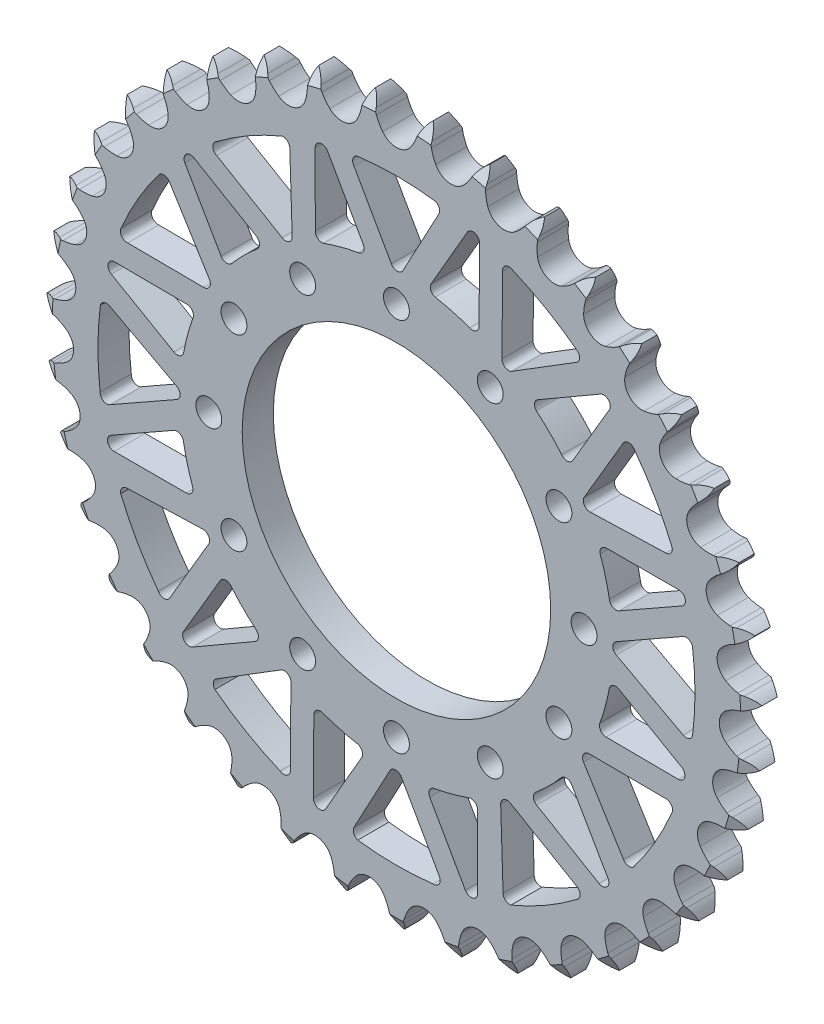
SolidWorks part; units mm, degrees
material "7075-T6 (SN)"
ref_plane "Front Plane" through (0, 0, 0) normal (0, 0, 1) x (1, 0, 0)
ref_plane "Top Plane" through (0, 0, 0) normal (0, 1, 0) x (1, 0, 0)
ref_plane "Right Plane" through (0, 0, 0) normal (1, 0, 0) x (0, 0, -1)
sketch "Work Sketch" plane through (0, 0, 0) normal (0, 0, 1) x (1, 0, 0)
  line L0 (0, 0) -> (0, 160.4542) construction
  line L1 (-112.0919, 78.9148) -> (87.2579, 78.9148) construction
  line L2 (5.102, 120.8822) -> (5.102, 112.9699) construction
  line L3 (-12.8497, 82.6953) -> (16.7256, 82.6953) construction
  line L4 (5.102, 82.6953) -> (-6.0879, 74.4036) construction
  line L5 (5.102, 82.6953) -> (-4.6505, 79.1506) construction
  line L6 (-4.6505, 79.1506) -> (-6.8863, 85.3019)
  line L7 (-11.5114, 78.0206) -> (-7.1525, 78.0206) construction
  line L8 (-11.0765, 124.7602) -> (-11.0765, 110.2345) construction
  line L9 (0, 0) -> (-3.4402, 42.6146) construction
  circle A0 centre (0, 0) radius 78.9148
  circle A1 centre (0, 78.9148) radius 4.0088
  arc A2 (-4.6505, 79.1506) -> (-3.2209, 76.5281) centre (5.0804, 82.7541) ccw
  circle A3 centre (-11.0765, 78.0206) radius 6.4254
  point P23 (-3.2209, 76.5281)
  dimension "D1" = 157.8295
  dimension "D8" = 10.3767
  dimension "D2" = 8.0177
  dimension "D3" = 5.102
  dimension "D4" = 3.7806
  dimension "D5" = 36.538
  dimension "D6" = 16.564
  dimension "D7" = 10.3767
  dimension "D9" = 0.8942
  dimension "D10" = 11.0765
  dimension "D11" = 4.615
sketch "Teeth Sketch" plane through (0, 0, 0) normal (0, 0, 1) x (1, 0, 0)
  line L0 (5.0376, 80.2155) -> (4.6505, 79.1506)
  line L1 (-7.4865, 92.7372) -> (-4.7839, 59.2593) construction
  line L2 (0, 0) -> (-10.9133, 132.3061) construction
  line L3 (7.8951, 79.9848) -> (8.1063, 78.8717)
  line L4 (16093.3137, -199351.4616) -> (-16096.7539, 199394.0762) construction
  line L5 (0, 146.3285) -> (0, 56.9858) construction
  line L6 (17.8398, 78.3686) -> (17.287, 77.3797)
  line L7 (0, -200000) -> (0, 200160.4542) construction
  line L8 (20.6234, 77.6826) -> (20.6533, 76.5499)
  line L9 (-4.6505, 79.1506) -> (-6.8863, 85.3019) construction
  line L10 (44.1616, 67.154) -> (43.8313, 66.0702)
  line L11 (-5.0376, 80.2155) -> (-4.6505, 79.1506)
  line L12 (30.18, 74.4921) -> (29.4757, 73.6046)
  line L13 (32.8175, 73.3684) -> (32.6653, 72.2456)
  line L14 (41.7385, 68.6862) -> (40.901, 67.9232)
  line L15 (52.2161, 61.1014) -> (51.267, 60.4826)
  line L16 (54.362, 59.2003) -> (53.8621, 58.1836)
  line L17 (61.3413, 51.9341) -> (60.3052, 51.4756)
  line L18 (63.1544, 49.7134) -> (62.4979, 48.79)
  line L19 (68.8777, 41.4218) -> (67.7815, 41.1354)
  line L20 (70.3112, 38.939) -> (69.515, 38.1328)
  line L21 (74.6303, 29.8366) -> (73.5023, 29.7298)
  line L22 (75.6469, 27.156) -> (74.7318, 26.488)
  line L23 (78.45, 17.4787) -> (77.3195, 17.5542)
  line L24 (79.0234, 14.6698) -> (78.013, 14.1572)
  line L25 (80.2378, 4.6681) -> (79.1341, 4.9239)
  line L26 (80.3533, 1.8035) -> (79.2737, 1.4597)
  line L27 (79.9476, -8.2634) -> (78.8992, -7.8338)
  line L28 (79.602, -11.1094) -> (78.4813, -11.2756)
  line L29 (77.5867, -20.9809) -> (76.6208, -20.3887)
  line L30 (76.7891, -23.7346) -> (75.6562, -23.7189)
  line L31 (73.2164, -33.155) -> (72.358, -32.4155)
  line L32 (71.9874, -35.7451) -> (70.8717, -35.5478)
  line L33 (66.9499, -44.4704) -> (66.2212, -43.6028)
  line L34 (65.3213, -46.8298) -> (64.2517, -46.4561)
  line L35 (58.9493, -54.634) -> (58.3693, -53.6608)
  line L36 (56.9634, -56.7016) -> (55.9676, -56.1612)
  line L37 (49.422, -63.3827) -> (49.0056, -62.329)
  line L38 (47.1301, -65.1049) -> (46.2339, -64.4118)
  line L39 (38.6147, -70.4897) -> (38.3727, -69.3829)
  line L40 (36.0763, -71.822) -> (35.3028, -70.9941)
  line L41 (26.8073, -75.7712) -> (26.746, -74.6398)
  line L42 (24.088, -76.679) -> (23.4574, -75.7377)
  line L43 (14.3056, -79.0901) -> (14.4266, -77.9636)
  line L44 (11.4759, -79.55) -> (11.0044, -78.5198)
  line L45 (1.4334, -80.3607) -> (1.7335, -79.2682)
  line L46 (-1.4334, -80.3607) -> (-1.7335, -79.2682)
  line L47 (-11.4759, -79.55) -> (-11.0044, -78.5198)
  line L48 (-14.3056, -79.0901) -> (-14.4266, -77.9636)
  line L49 (-24.088, -76.679) -> (-23.4574, -75.7377)
  line L50 (-26.8073, -75.7712) -> (-26.746, -74.6398)
  line L51 (-36.0763, -71.822) -> (-35.3028, -70.9941)
  line L52 (-38.6147, -70.4897) -> (-38.3727, -69.3829)
  line L53 (-47.1301, -65.1049) -> (-46.2339, -64.4118)
  line L54 (-49.422, -63.3827) -> (-49.0056, -62.329)
  line L55 (-56.9634, -56.7016) -> (-55.9676, -56.1612)
  line L56 (-58.9493, -54.634) -> (-58.3693, -53.6608)
  line L57 (-65.3213, -46.8298) -> (-64.2517, -46.4561)
  line L58 (-66.9499, -44.4704) -> (-66.2212, -43.6028)
  line L59 (-71.9874, -35.7451) -> (-70.8717, -35.5478)
  line L60 (-73.2164, -33.155) -> (-72.358, -32.4155)
  line L61 (-76.7891, -23.7346) -> (-75.6562, -23.7189)
  line L62 (-77.5867, -20.9809) -> (-76.6208, -20.3887)
  line L63 (-79.602, -11.1094) -> (-78.4813, -11.2756)
  line L64 (-79.9476, -8.2634) -> (-78.8992, -7.8338)
  line L65 (-80.3533, 1.8035) -> (-79.2737, 1.4597)
  line L66 (-80.2378, 4.6681) -> (-79.1341, 4.9239)
  line L67 (-79.0234, 14.6698) -> (-78.013, 14.1572)
  line L68 (-78.45, 17.4787) -> (-77.3195, 17.5542)
  line L69 (-75.6469, 27.156) -> (-74.7318, 26.488)
  line L70 (-74.6303, 29.8366) -> (-73.5023, 29.7298)
  line L71 (-70.3112, 38.939) -> (-69.515, 38.1328)
  line L72 (-68.8777, 41.4218) -> (-67.7815, 41.1354)
  line L73 (-63.1544, 49.7134) -> (-62.4979, 48.79)
  line L74 (-61.3413, 51.9341) -> (-60.3052, 51.4756)
  line L75 (-54.362, 59.2003) -> (-53.8621, 58.1836)
  line L76 (-52.2161, 61.1014) -> (-51.267, 60.4826)
  line L77 (-44.1616, 67.154) -> (-43.8313, 66.0702)
  line L78 (-41.7385, 68.6862) -> (-40.901, 67.9232)
  line L79 (-32.8175, 73.3684) -> (-32.6653, 72.2456)
  line L80 (-30.18, 74.4921) -> (-29.4757, 73.6046)
  line L81 (-20.6234, 77.6826) -> (-20.6533, 76.5499)
  line L82 (-17.8398, 78.3686) -> (-17.287, 77.3797)
  line L83 (-7.8951, 79.9848) -> (-8.1063, 78.8717)
  arc A0 (-6.8336, 82.8459) -> (-5.0376, 80.2155) centre (-11.0765, 78.0206) cw
  circle A1 centre (-11.0765, 78.0206) radius 6.4254 construction
  arc A2 (-3.2209, 76.5281) -> (-4.6505, 79.1506) centre (5.0804, 82.7541) cw
  arc A3 (-4.6505, 79.1506) -> (-3.2209, 76.5281) centre (5.0804, 82.7541) ccw construction
  circle A4 centre (0, 78.9148) radius 4.0088 construction
  arc A5 (-3.2209, 76.5281) -> (3.2209, 76.5281) centre (0, 78.9148) ccw
  arc A6 (3.2209, 76.5281) -> (4.6505, 79.1506) centre (-5.0804, 82.7541) ccw
  arc A7 (6.8336, 82.8459) -> (5.0376, 80.2155) centre (11.0765, 78.0206) ccw
  arc A8 (6.5443, 82.8692) -> (7.8951, 79.9848) centre (1.5824, 78.787) cw
  arc A9 (9.0967, 76.0537) -> (8.1063, 78.8717) centre (18.2893, 80.8676) cw
  arc A10 (9.0967, 76.0537) -> (15.4552, 75.0204) centre (12.6588, 77.8928) ccw
  arc A11 (15.4552, 75.0204) -> (17.287, 77.3797) centre (8.2601, 82.4975) ccw
  arc A12 (20.0345, 80.6769) -> (17.8398, 78.3686) centre (23.4484, 75.2334) ccw
  arc A13 (19.7528, 80.7463) -> (20.6234, 77.6826) centre (14.2002, 77.5129) cw
  arc A14 (21.1788, 73.6096) -> (20.6533, 76.5499) centre (31.0245, 76.8865) cw
  arc A15 (21.1788, 73.6096) -> (27.2892, 71.5697) centre (24.9898, 74.8535) ccw
  arc A16 (27.2892, 71.5697) -> (29.4757, 73.6046) centre (21.3867, 80.1041) ccw
  arc A17 (32.7165, 76.4184) -> (30.18, 74.4921) centre (35.2131, 70.4978) ccw
  arc A18 (32.4496, 76.5321) -> (32.8175, 73.3684) centre (26.4502, 74.2313) cw
  arc A19 (32.7124, 69.2591) -> (32.6653, 72.2456) centre (42.9562, 70.9142) cw
  arc A20 (32.7124, 69.2591) -> (38.4163, 66.2654) centre (36.6735, 69.8756) ccw
  arc A21 (38.4163, 66.2654) -> (40.901, 67.9232) centre (33.9593, 75.6361) ccw
  arc A22 (44.5512, 70.1807) -> (41.7385, 68.6862) centre (46.0657, 63.9363) ccw
  arc A23 (44.306, 70.3358) -> (44.1616, 67.154) centre (38.0153, 69.0271) cw
  arc A24 (43.3987, 63.1147) -> (43.8313, 66.0702) centre (53.7754, 63.1052) cw
  arc A25 (43.3987, 63.1147) -> (48.5486, 59.2448) centre (47.4074, 63.0878) ccw
  arc A26 (48.5486, 59.2448) -> (51.267, 60.4826) centre (45.6524, 69.2092) ccw
  arc A27 (55.2321, 62.1253) -> (52.2161, 61.1014) centre (55.7253, 55.7189) ccw
  arc A28 (55.0149, 62.3178) -> (54.362, 59.2003) centre (48.5957, 62.0351) cw
  arc A29 (52.961, 55.3358) -> (53.8621, 58.1836) centre (63.2018, 53.6618) cw
  arc A30 (52.961, 55.3358) -> (57.4234, 50.6899) centre (56.9135, 54.6662) ccw
  arc A31 (57.4234, 50.6899) -> (60.3052, 51.4756) centre (56.1632, 60.9898) ccw
  arc A32 (64.4824, 52.461) -> (61.3413, 51.9341) centre (63.9416, 46.0584) ccw
  arc A33 (64.2989, 52.6858) -> (63.1544, 49.7134) centre (57.9175, 53.4365) cw
  arc A34 (61.1517, 46.1237) -> (62.4979, 48.79) centre (70.9913, 42.8287) cw
  arc A35 (61.1517, 46.1237) -> (64.811, 40.8221) centre (64.9456, 44.8287) ccw
  arc A36 (64.811, 40.8221) -> (67.7815, 41.1354) centre (65.2193, 51.1908) ccw
  arc A37 (72.0627, 41.4379) -> (68.8777, 41.4218) centre (70.5018, 35.205) ccw
  arc A38 (71.9177, 41.6892) -> (70.3112, 38.939) centre (65.7393, 43.4539) cw
  arc A39 (67.7585, 35.717) -> (69.515, 38.1328) centre (76.9422, 30.8862) cw
  arc A40 (67.7585, 35.717) -> (70.5201, 29.8971) centre (71.2956, 33.8302) ccw
  arc A41 (70.5201, 29.8971) -> (73.5023, 29.7298) centre (72.5864, 40.0659) ccw
  arc A42 (77.7767, 29.3416) -> (74.6303, 29.8366) centre (75.2361, 23.4398) ccw
  arc A43 (77.6738, 29.6129) -> (75.6469, 27.156) centre (71.8585, 32.3458) cw
  arc A44 (72.6105, 24.3852) -> (74.7318, 26.488) centre (80.9003, 18.1439) cw
  arc A45 (72.6105, 24.3852) -> (74.4027, 18.1977) centre (75.7991, 21.9555) ccw
  arc A46 (74.4027, 18.1977) -> (77.3195, 17.5542) centre (78.0734, 27.9034) ccw
  arc A47 (81.4762, 16.4854) -> (78.45, 17.4787) centre (78.0218, 11.0675) ccw
  arc A48 (81.4182, 16.7697) -> (79.0234, 14.6698) centre (76.1166, 20.4) cw
  arc A49 (75.5818, 12.4219) -> (78.013, 14.1572) centre (82.7631, 4.9316) cw
  arc A50 (75.5818, 12.4219) -> (76.3583, 6.027) centre (78.3394, 9.5121) ccw
  arc A51 (76.3583, 6.027) -> (79.1341, 4.9239) centre (81.5384, 15.0182) ccw
  arc A52 (83.0656, 3.2022) -> (80.2378, 4.6681) centre (78.7868, -1.5914) ccw
  arc A53 (83.0539, 3.4922) -> (80.3533, 1.8035) centre (78.4033, 7.9259) cw
  arc A54 (76.5957, 0.1368) -> (79.2737, 1.4597) centre (82.4825, -8.4084) cw
  arc A55 (76.5957, 0.1368) -> (76.3363, -6.2998) centre (78.8508, -3.1776) ccw
  arc A56 (76.3363, -6.2998) -> (78.8992, -7.8338) centre (82.8916, 1.7441) ccw
  arc A57 (82.5035, -10.1639) -> (79.9476, -8.2634) centre (77.5113, -14.2091) ccw
  arc A58 (82.5385, -9.8758) -> (79.602, -11.1094) centre (78.6594, -4.7535) cw
  arc A59 (75.6257, -12.1517) -> (78.4813, -11.2756) centre (80.0655, -21.5307) cw
  arc A60 (75.6257, -12.1517) -> (74.3372, -18.4634) centre (77.3199, -15.785) ccw
  arc A61 (74.3372, -18.4634) -> (76.6208, -20.3887) centre (82.0979, -11.5753) ccw
  arc A62 (79.8047, -23.2668) -> (77.5867, -20.9809) centre (74.2283, -26.4587) ccw
  arc A63 (79.8855, -22.9881) -> (76.7891, -23.7346) centre (76.8783, -17.3098) cw
  arc A64 (72.6971, -24.1256) -> (75.6562, -23.7189) centre (75.5749, -34.0953) cw
  arc A65 (72.6971, -24.1256) -> (70.4128, -30.1488) centre (73.7866, -27.9836) ccw
  arc A66 (70.4128, -30.1488) -> (72.358, -32.4155) centre (79.178, -24.5948) ccw
  arc A67 (75.039, -35.7671) -> (73.2164, -33.155) centre (69.0227, -38.0232) ccw
  arc A68 (75.1634, -35.5049) -> (71.9874, -35.7451) centre (73.106, -29.4178) cw
  arc A69 (67.8857, -35.4746) -> (70.8717, -35.5478) centre (69.127, -45.7768) cw
  arc A70 (67.8857, -35.4746) -> (64.6648, -41.0534) centre (68.3422, -39.4574) ccw
  arc A71 (64.6648, -41.0534) -> (66.2212, -43.6028) centre (74.2074, -36.9773) ccw
  arc A72 (68.3299, -47.341) -> (66.9499, -44.4704) centre (62.0296, -48.6028) ccw
  arc A73 (68.4947, -47.1022) -> (65.3213, -46.8298) centre (67.4404, -40.7639) cw
  arc A74 (61.3161, -45.9049) -> (64.2517, -46.4561) centre (60.8887, -56.2728) cw
  arc A75 (61.3161, -45.9049) -> (57.2419, -50.8948) centre (61.1278, -49.9093) ccw
  arc A76 (57.2419, -50.8948) -> (58.3693, -53.6608) centre (67.3148, -48.4022) ccw
  arc A77 (59.851, -57.6888) -> (58.9493, -54.634) centre (53.4299, -57.9236) ccw
  arc A78 (60.052, -57.4796) -> (56.9634, -56.7016) centre (60.0281, -51.0542) cw
  arc A79 (53.1584, -55.1462) -> (55.9676, -56.1612) centre (51.0734, -65.3113) cw
  arc A80 (53.1584, -55.1462) -> (48.3366, -59.4179) centre (52.3302, -59.0685) ccw
  arc A81 (48.3366, -59.4179) -> (49.0056, -62.329) centre (58.6789, -58.5735) ccw
  arc A82 (49.822, -66.5425) -> (49.422, -63.3827) centre (43.4464, -65.7443) ccw
  arc A83 (50.054, -66.3682) -> (47.1301, -65.1049) centre (51.0611, -60.0222) cw
  arc A84 (43.6239, -62.9593) -> (46.2339, -64.4118) centre (39.9354, -72.6583) cw
  arc A85 (43.6239, -62.9593) -> (38.1793, -66.4022) centre (42.1772, -66.698) ccw
  arc A86 (38.1793, -66.4022) -> (38.3727, -69.3829) centre (48.5231, -67.2277) ccw
  arc A87 (38.5026, -73.6728) -> (38.6147, -70.4897) centre (32.3376, -71.8622) ccw
  arc A88 (38.7596, -73.538) -> (36.0763, -71.822) centre (40.7716, -67.4357) cw
  arc A89 (32.9596, -69.1417) -> (35.3028, -70.9941) centre (27.763, -78.1234) cw
  arc A90 (32.9596, -69.1417) -> (27.0333, -71.6667) centre (30.932, -72.6) ccw
  arc A91 (27.0333, -71.6667) -> (26.746, -74.6398) centre (37.1107, -74.1408) ccw
  arc A92 (26.1861, -78.8951) -> (26.8073, -75.7712) centre (20.3913, -76.1189) ccw
  arc A93 (26.4613, -78.8032) -> (24.088, -76.679) centre (29.4261, -73.1027) cw
  arc A94 (21.4417, -73.5335) -> (23.4574, -75.7377) centre (14.8716, -81.5653) cw
  arc A95 (21.4417, -73.5335) -> (15.187, -75.0751) centre (18.8855, -76.6216) ccw
  arc A96 (15.187, -75.0751) -> (14.4266, -77.9636) centre (24.7371, -79.1336) ccw
  arc A97 (13.1913, -82.0739) -> (14.3056, -79.0901) centre (7.9169, -78.4042) ccw
  arc A98 (13.4777, -82.0274) -> (11.4759, -79.55) centre (17.3186, -76.8763) cw
  arc A99 (9.3684, -76.0207) -> (11.0044, -78.5198) centre (1.595, -82.8946) cw
  arc A100 (9.3684, -76.0207) -> (2.9475, -76.5391) centre (6.35, -78.6589) ccw
  arc A101 (2.9475, -76.5391) -> (1.7335, -79.2682) centre (11.7228, -82.077) ccw
  arc A102 (-0.1451, -83.1271) -> (1.4334, -80.3607) centre (-4.7625, -78.6589) ccw
  arc A103 (0.1451, -83.1271) -> (-1.4334, -80.3607) centre (4.7625, -78.6589) cw
  arc A104 (-2.9475, -76.5391) -> (-1.7335, -79.2682) centre (-11.7228, -82.077) cw
  arc A105 (-2.9475, -76.5391) -> (-9.3684, -76.0207) centre (-6.35, -78.6589) ccw
  arc A106 (-9.3684, -76.0207) -> (-11.0044, -78.5198) centre (-1.595, -82.8946) ccw
  arc A107 (-13.4777, -82.0274) -> (-11.4759, -79.55) centre (-17.3186, -76.8763) ccw
  arc A108 (-13.1913, -82.0739) -> (-14.3056, -79.0901) centre (-7.9169, -78.4042) cw
  arc A109 (-15.187, -75.0751) -> (-14.4266, -77.9636) centre (-24.7371, -79.1336) cw
  arc A110 (-15.187, -75.0751) -> (-21.4417, -73.5335) centre (-18.8855, -76.6216) ccw
  arc A111 (-21.4417, -73.5335) -> (-23.4574, -75.7377) centre (-14.8716, -81.5653) ccw
  arc A112 (-26.4613, -78.8032) -> (-24.088, -76.679) centre (-29.4261, -73.1027) ccw
  arc A113 (-26.1861, -78.8951) -> (-26.8073, -75.7712) centre (-20.3913, -76.1189) cw
  arc A114 (-27.0333, -71.6667) -> (-26.746, -74.6398) centre (-37.1107, -74.1408) cw
  arc A115 (-27.0333, -71.6667) -> (-32.9596, -69.1417) centre (-30.932, -72.6) ccw
  arc A116 (-32.9596, -69.1417) -> (-35.3028, -70.9941) centre (-27.763, -78.1234) ccw
  arc A117 (-38.7596, -73.538) -> (-36.0763, -71.822) centre (-40.7716, -67.4357) ccw
  arc A118 (-38.5026, -73.6728) -> (-38.6147, -70.4897) centre (-32.3376, -71.8622) cw
  arc A119 (-38.1793, -66.4022) -> (-38.3727, -69.3829) centre (-48.5231, -67.2277) cw
  arc A120 (-38.1793, -66.4022) -> (-43.6239, -62.9593) centre (-42.1772, -66.698) ccw
  arc A121 (-43.6239, -62.9593) -> (-46.2339, -64.4118) centre (-39.9354, -72.6583) ccw
  arc A122 (-50.054, -66.3682) -> (-47.1301, -65.1049) centre (-51.0611, -60.0222) ccw
  arc A123 (-49.822, -66.5425) -> (-49.422, -63.3827) centre (-43.4464, -65.7443) cw
  arc A124 (-48.3366, -59.4179) -> (-49.0056, -62.329) centre (-58.6789, -58.5735) cw
  arc A125 (-48.3366, -59.4179) -> (-53.1584, -55.1462) centre (-52.3302, -59.0685) ccw
  arc A126 (-53.1584, -55.1462) -> (-55.9676, -56.1612) centre (-51.0734, -65.3113) ccw
  arc A127 (-60.052, -57.4796) -> (-56.9634, -56.7016) centre (-60.0281, -51.0542) ccw
  arc A128 (-59.851, -57.6888) -> (-58.9493, -54.634) centre (-53.4299, -57.9236) cw
  arc A129 (-57.2419, -50.8948) -> (-58.3693, -53.6608) centre (-67.3148, -48.4022) cw
  arc A130 (-57.2419, -50.8948) -> (-61.3161, -45.9049) centre (-61.1278, -49.9093) ccw
  arc A131 (-61.3161, -45.9049) -> (-64.2517, -46.4561) centre (-60.8887, -56.2728) ccw
  arc A132 (-68.4947, -47.1022) -> (-65.3213, -46.8298) centre (-67.4404, -40.7639) ccw
  arc A133 (-68.3299, -47.341) -> (-66.9499, -44.4704) centre (-62.0296, -48.6028) cw
  arc A134 (-64.6648, -41.0534) -> (-66.2212, -43.6028) centre (-74.2074, -36.9773) cw
  arc A135 (-64.6648, -41.0534) -> (-67.8857, -35.4746) centre (-68.3422, -39.4574) ccw
  arc A136 (-67.8857, -35.4746) -> (-70.8717, -35.5478) centre (-69.127, -45.7768) ccw
  arc A137 (-75.1634, -35.5049) -> (-71.9874, -35.7451) centre (-73.106, -29.4178) ccw
  arc A138 (-75.039, -35.7671) -> (-73.2164, -33.155) centre (-69.0227, -38.0232) cw
  arc A139 (-70.4128, -30.1488) -> (-72.358, -32.4155) centre (-79.178, -24.5948) cw
  arc A140 (-70.4128, -30.1488) -> (-72.6971, -24.1256) centre (-73.7866, -27.9836) ccw
  arc A141 (-72.6971, -24.1256) -> (-75.6562, -23.7189) centre (-75.5749, -34.0953) ccw
  arc A142 (-79.8855, -22.9881) -> (-76.7891, -23.7346) centre (-76.8783, -17.3098) ccw
  arc A143 (-79.8047, -23.2668) -> (-77.5867, -20.9809) centre (-74.2283, -26.4587) cw
  arc A144 (-74.3372, -18.4634) -> (-76.6208, -20.3887) centre (-82.0979, -11.5753) cw
  arc A145 (-74.3372, -18.4634) -> (-75.6257, -12.1517) centre (-77.3199, -15.785) ccw
  arc A146 (-75.6257, -12.1517) -> (-78.4813, -11.2756) centre (-80.0655, -21.5307) ccw
  arc A147 (-82.5385, -9.8758) -> (-79.602, -11.1094) centre (-78.6594, -4.7535) ccw
  arc A148 (-82.5035, -10.1639) -> (-79.9476, -8.2634) centre (-77.5113, -14.2091) cw
  arc A149 (-76.3363, -6.2998) -> (-78.8992, -7.8338) centre (-82.8916, 1.7441) cw
  arc A150 (-76.3363, -6.2998) -> (-76.5957, 0.1368) centre (-78.8508, -3.1776) ccw
  arc A151 (-76.5957, 0.1368) -> (-79.2737, 1.4597) centre (-82.4825, -8.4084) ccw
  arc A152 (-83.0539, 3.4922) -> (-80.3533, 1.8035) centre (-78.4033, 7.9259) ccw
  arc A153 (-83.0656, 3.2022) -> (-80.2378, 4.6681) centre (-78.7868, -1.5914) cw
  arc A154 (-76.3583, 6.027) -> (-79.1341, 4.9239) centre (-81.5384, 15.0182) cw
  arc A155 (-76.3583, 6.027) -> (-75.5818, 12.4219) centre (-78.3394, 9.5121) ccw
  arc A156 (-75.5818, 12.4219) -> (-78.013, 14.1572) centre (-82.7631, 4.9316) ccw
  arc A157 (-81.4182, 16.7697) -> (-79.0234, 14.6698) centre (-76.1166, 20.4) ccw
  arc A158 (-81.4762, 16.4854) -> (-78.45, 17.4787) centre (-78.0218, 11.0675) cw
  arc A159 (-74.4027, 18.1977) -> (-77.3195, 17.5542) centre (-78.0734, 27.9034) cw
  arc A160 (-74.4027, 18.1977) -> (-72.6105, 24.3852) centre (-75.7991, 21.9555) ccw
  arc A161 (-72.6105, 24.3852) -> (-74.7318, 26.488) centre (-80.9003, 18.1439) ccw
  arc A162 (-77.6738, 29.6129) -> (-75.6469, 27.156) centre (-71.8585, 32.3458) ccw
  arc A163 (-77.7767, 29.3416) -> (-74.6303, 29.8366) centre (-75.2361, 23.4398) cw
  arc A164 (-70.5201, 29.8971) -> (-73.5023, 29.7298) centre (-72.5864, 40.0659) cw
  arc A165 (-70.5201, 29.8971) -> (-67.7585, 35.717) centre (-71.2956, 33.8302) ccw
  arc A166 (-67.7585, 35.717) -> (-69.515, 38.1328) centre (-76.9422, 30.8862) ccw
  arc A167 (-71.9177, 41.6892) -> (-70.3112, 38.939) centre (-65.7393, 43.4539) ccw
  arc A168 (-72.0627, 41.4379) -> (-68.8777, 41.4218) centre (-70.5018, 35.205) cw
  arc A169 (-64.811, 40.8221) -> (-67.7815, 41.1354) centre (-65.2193, 51.1908) cw
  arc A170 (-64.811, 40.8221) -> (-61.1517, 46.1237) centre (-64.9456, 44.8287) ccw
  arc A171 (-61.1517, 46.1237) -> (-62.4979, 48.79) centre (-70.9913, 42.8287) ccw
  arc A172 (-64.2989, 52.6858) -> (-63.1544, 49.7134) centre (-57.9175, 53.4365) ccw
  arc A173 (-64.4824, 52.461) -> (-61.3413, 51.9341) centre (-63.9416, 46.0584) cw
  arc A174 (-57.4234, 50.6899) -> (-60.3052, 51.4756) centre (-56.1632, 60.9898) cw
  arc A175 (-57.4234, 50.6899) -> (-52.961, 55.3358) centre (-56.9135, 54.6662) ccw
  arc A176 (-52.961, 55.3358) -> (-53.8621, 58.1836) centre (-63.2018, 53.6618) ccw
  arc A177 (-55.0149, 62.3178) -> (-54.362, 59.2003) centre (-48.5957, 62.0351) ccw
  arc A178 (-55.2321, 62.1253) -> (-52.2161, 61.1014) centre (-55.7253, 55.7189) cw
  arc A179 (-48.5486, 59.2448) -> (-51.267, 60.4826) centre (-45.6524, 69.2092) cw
  arc A180 (-48.5486, 59.2448) -> (-43.3987, 63.1147) centre (-47.4074, 63.0878) ccw
  arc A181 (-43.3987, 63.1147) -> (-43.8313, 66.0702) centre (-53.7754, 63.1052) ccw
  arc A182 (-44.306, 70.3358) -> (-44.1616, 67.154) centre (-38.0153, 69.0271) ccw
  arc A183 (-44.5512, 70.1807) -> (-41.7385, 68.6862) centre (-46.0657, 63.9363) cw
  arc A184 (-38.4163, 66.2654) -> (-40.901, 67.9232) centre (-33.9593, 75.6361) cw
  arc A185 (-38.4163, 66.2654) -> (-32.7124, 69.2591) centre (-36.6735, 69.8756) ccw
  arc A186 (-32.7124, 69.2591) -> (-32.6653, 72.2456) centre (-42.9562, 70.9142) ccw
  arc A187 (-32.4496, 76.5321) -> (-32.8175, 73.3684) centre (-26.4502, 74.2313) ccw
  arc A188 (-32.7165, 76.4184) -> (-30.18, 74.4921) centre (-35.2131, 70.4978) cw
  arc A189 (-27.2892, 71.5697) -> (-29.4757, 73.6046) centre (-21.3867, 80.1041) cw
  arc A190 (-27.2892, 71.5697) -> (-21.1788, 73.6096) centre (-24.9898, 74.8535) ccw
  arc A191 (-21.1788, 73.6096) -> (-20.6533, 76.5499) centre (-31.0245, 76.8865) ccw
  arc A192 (-19.7528, 80.7463) -> (-20.6234, 77.6826) centre (-14.2002, 77.5129) ccw
  arc A193 (-20.0345, 80.6769) -> (-17.8398, 78.3686) centre (-23.4484, 75.2334) cw
  arc A194 (-15.4552, 75.0204) -> (-17.287, 77.3797) centre (-8.2601, 82.4975) cw
  arc A195 (-15.4552, 75.0204) -> (-9.0967, 76.0537) centre (-12.6588, 77.8928) ccw
  arc A196 (-9.0967, 76.0537) -> (-8.1063, 78.8717) centre (-18.2893, 80.8676) ccw
  arc A197 (-6.5443, 82.8692) -> (-7.8951, 79.9848) centre (-1.5824, 78.787) ccw
  point P77 (0, 0)
  dimension "D1" = 4.615
  dimension "D2" = 4.715
  dimension "D3" = 39
extrude "Extrusion" add sketch "Teeth Sketch" along normal blind 7.2136 contours A0 region at (0, 0, 0)
sketch "Sketch1" plane through (0, 0, 0) normal (0, 0, -1) x (-1, 0, 0)
  circle A0 centre (0, 0) radius 78.9443
  circle A1 centre (0, 0) radius 35.7643
  dimension "D1" = 43.18
extrude "Cut-Extrude" cut sketch "Sketch1" against normal through all both and the other way through all contours A1
ref_axis "Axis1" [suppressed] through (0, 0, 7.2136) along (0, 0, -1)
ref_plane "Sprocket Center Plane" through (0, 0, 3.6068) normal (0, 0, 1) x (1, 0, 0)
sketch "Pitch Circle" plane through (0, 0, 3.6068) normal (0, 0, -1) x (-1, 0, 0)
  circle A0 centre (0, 0) radius 82.9531 construction
  dimension "D1" = 165.9063
sketch "Chain Pitch Circle" plane through (0, 0, 0) normal (0, 0, -1) x (-1, 0, 0)
  circle A0 centre (0, 0) radius 82.9531 construction
  dimension "D1" = 165.9063
ref_plane "Center Plane" through (0, 0, 3.6068) normal (0, 0, 1) x (1, 0, 0)
hole_wizard "Ø6.0mm Dowel Hole1" positions "Sketch7" profile "Sketch8" hole size "Ø6.0" standard "ANSI Metric" end condition through all
sketch "Sketch7" plane through (0, 0, 7.2136) normal (0, 0, 1) x (1, 0, 0)
  point P0 (-43.5, 0)
  dimension "D1" = 43.5
sketch "Sketch8" plane through (-43.5, 0, 7.2136) normal (1, 0, 0) x (0, -1, 0)
  line L0 (0, 0) -> (0, 7.2136)
  line L1 (0, 7.2136) -> (3, 7.2136)
  line L2 (3, 7.2136) -> (3, 0)
  line L5 (3, 0) -> (0, 0)
  line L11 (0, -6.35) -> (0, 107.95) construction
  dimension "Thru Hole Dia." = 6
  dimension "Thru Hole Depth" = 7.2136
pattern_circular "CirPattern1" count 12 over 360 about axis through (0, 0, 7.2136) along (0, 0, -1) of "Ø6.0mm Dowel Hole1" reverse direction yes
sketch "Sketch5" plane through (0, 0, 0) normal (1, 0, 0) x (0, 0, -1)
  line L0 (-1.8288, -82.9722) -> (-5.3848, -82.9722)
  line L3 (-5.3848, -79.7786) -> (-7.2136, -79.7786)
  line L5 (-7.2136, -79.7786) -> (-7.2136, -82.9722)
  line L6 (-7.2136, -82.9722) -> (-5.3848, -82.9722)
  line L7 (-7.2136, -82.9722) -> (0, -82.9722) construction
  line L8 (-7.2136, -82.9722) -> (0, -82.9722)
  line L9 (-5.3848, -82.9722) -> (-7.2136, -79.7786)
  line L10 (-5.3848, -79.7786) -> (-5.3848, -82.9722)
  point P5 (-3.6068, -82.9722)
  dimension "D1" = 3.556
  dimension "D2" = 3.1936
  dimension "D3" = 1.8288
revolve "Cut-Revolve1" cut sketch "Sketch5" angle 360 about axis through (0, 0, 7.2136) along (0, 0, -1) region at (0, -81.9076, 6.604)
mirror "Mirror1" about plane through (0, 0, 3.6068) normal (0, 0, 1) of "Cut-Revolve1"
sketch "Sketch9" plane through (0, 0, 7.2136) normal (0, 0, 1) x (1, 0, 0)
  line L5 (0, 0) -> (-29.9262, 113.2202) construction
  line L9 (-18.8193, 48.7004) -> (-18.8298, 65.4724)
  line L10 (-15.9804, 66.2256) -> (-7.7022, 51.6389)
  line L13 (9.8257, 66.469) -> (1.5186, 50.9613)
  line L14 (-1.173, 50.9705) -> (-9.8561, 66.2707)
  line L15 (0, 0) -> (0.2325, 68.5791) construction
  circle A0 centre (0, 0) radius 51.6812 construction
  arc A1 (1.5186, 50.9613) -> (-1.173, 50.9705) centre (0.1752, 51.681) cw
  arc A2 (8.9755, 68.6306) -> (9.8257, 66.469) centre (8.4823, 67.1886) cw
  arc A3 (-8.5099, 68.6899) -> (-9.8561, 66.2707) centre (-8.626, 67.1703) ccw
  arc A4 (-18.8298, 65.4724) -> (-15.9804, 66.2256) centre (-17.3058, 65.4734) cw
  arc A5 (-7.7022, 51.6389) -> (-8.9117, 49.3671) centre (-9.0277, 50.8867) cw
  arc A6 (-18.8193, 48.7004) -> (-16.9303, 47.2217) centre (-17.2953, 48.7014) ccw
  circle A7 centre (0, 0) radius 67.7219 construction
  circle A8 centre (0, 0) radius 50.9839 construction
  circle A9 centre (0, 0) radius 68.1264 construction
  circle A10 centre (0, 0) radius 69.215 construction
  circle A11 centre (0, 0) radius 50.165 construction
  arc A12 (-16.9303, 47.2217) -> (-8.9117, 49.3671) centre (0, 0) cw
  arc A13 (-8.5099, 68.6899) -> (8.9755, 68.6306) centre (0, 0) cw
  point P5 (3, 43.5)
  point P6 (-12.9017, 65.4177)
  point P29 (-6.7363, 52.0578)
  point P30 (-14.5207, 64.9855)
  point P31 (0.1701, 50.157)
  point P32 (-12.6173, 68.0553)
  point P34 (1.7242, 41.045)
  point P35 (0.2347, 69.2146)
  point P36 (7.8691, 68.7662)
  point P37 (8.3568, 66.4794)
  point P38 (-11.02, 65.9985)
  point P39 (-9.8561, 66.2256)
  dimension "D3" = 1.524
  dimension "D4" = 69.215
  dimension "D2" = 50.165
  dimension "D6" = 15
extrude "Cut-Extrude1" cut sketch "Sketch9" against normal through all both and the other way through all
pattern_circular "CirPattern2" count 12 over 360 about axis through (0, 0, 7.2136) along (0, 0, -1) of "Cut-Extrude1" reverse direction yes
equation "\"P\"= 0.500'//Chain Pitch"
equation "\"N\"= 39'//Number of Teeth"
equation "\"Dr\"= 5 / 16'//Roller Diameter"
equation "\"Ds\"= 1.0005 * \"Dr\" + 0.003'Seating Curve DIameter"
equation "\"R\"= \"Ds\" / 2"
equation "\"A\"= 35 + 60 / \"N\""
equation "\"B\"= 18 - 56 / \"N\""
equation "\"ac\"= 0.8 * \"Dr\""
equation "\"M\"= 0.8 * \"Dr\" * cos ( 35 + 60 / \"N\" )"
equation "\"T\"= 0.8 * \"Dr\" * sin ( 35 + 60 / \"N\" )"
equation "\"E\"= 1.3025 * \"Dr\" + 0.0015"
equation "\"Chordal Length of Arc xy\"= ( 2.605 * \"Dr\" + 0.003 ) * sin ( 9 - 28 / \"N\" )"
equation "\"yz\"= \"Dr\" * ( 1.4 * sin ( 17 - 64 / \"N\" ) - 0.8 * sin ( 18 - 56 / \"N\" ) )"
equation "\"ab\"= 1.4 * \"Dr\""
equation "\"W\"= 1.4 * \"Dr\" * cos ( 180 / \"N\" )"
equation "\"V\"= 1.4 * \"Dr\" * sin ( 180 / \"N\" )"
equation "\"F\"= \"Dr\" * ( 0.8 * cos ( 18 - 56 / \"N\" ) + 1.4 * cos ( 17 - 64 / \"N\" ) - 1.3025 )"
equation "\"H\"= sqr ( \"F\" ^ 2 - ( 1.4 * \"Dr\" - \"P\" / 2 ) ^ 2 )"
equation "\"S\"= \"P\" / 2 * cos ( 180 / \"N\" ) + \"H\" * sin ( 180 / \"N\" )"
equation "\"PD\"= \"P\" / ( sin ( 180 / \"N\" ) )"
equation "\"D1@Work Sketch\" = \"PD\""
equation "\"D3@Work Sketch\" = \"M\""
equation "\"D4@Work Sketch\" = \"T\""
equation "\"D5@Work Sketch\" = \"A\""
equation "\"D6@Work Sketch\" = \"B\""
equation "\"D7@Work Sketch\" = \"E\""
equation "\"D8@Work Sketch\" = \"E\""
equation "\"D9@Work Sketch\" = \"V\""
equation "\"D10@Work Sketch\" = \"W\""
equation "\"D2@Work Sketch\" = \"R\" * 2"
equation "\"D11@Work Sketch\" = 180 / \"N\""
equation "\"D2@Teeth Sketch\" = 180 / \"N\" + 0.1"
equation "\"D3@Teeth Sketch\" = \"N\""
equation "\"Edge Thickness\"=1.7"
equation "\"D1@Sketch1\"=\"Edge Thickness\""
equation "\"ST\"= 0.284'//Sprocket Thickness"
